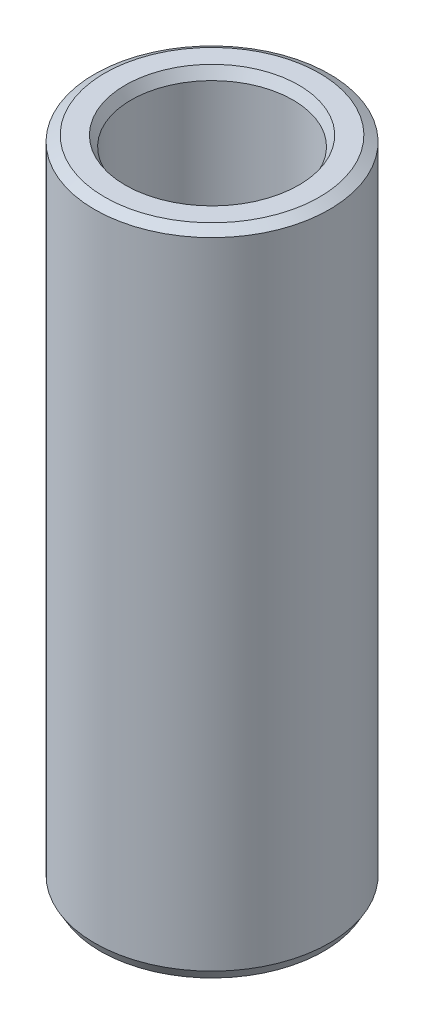
SolidWorks part; units mm, degrees
ref_plane "Front Plane" through (0, 0, 0) normal (0, 0, 1) x (1, 0, 0)
ref_plane "Top Plane" through (0, 0, 0) normal (0, 1, 0) x (1, 0, 0)
ref_plane "Right Plane" through (0, 0, 0) normal (1, 0, 0) x (0, 0, -1)
sketch "Sketch1" plane through (0, 0, 0) normal (0, 1, 0) x (1, 0, 0)
  circle A0 centre (0, 0) radius 57.5
  dimension "SLEEVE_OD" = 115
extrude "Boss-Extrude1" add sketch "Sketch1" along normal blind 318.8693
sketch "Sketch2" plane through (0, 0, 0) normal (0, 1, 0) x (1, 0, 0)
  circle A0 centre (0, 0) radius 39.6501
  dimension "BORE_D" = 79.3002
extrude "Cut-Extrude1" cut sketch "Sketch2" along normal through all
chamfer "Chamfer1" distance 2.8333 angle 60 4 edges at (0, 318.8693, 39.6501) (0, 0, 39.6501) (0, 0, 57.5) (0, 318.8693, 57.5) first distance on face at (0, 318.8693, 39.6501) first distance on face at (0, 0, 39.6501) first distance on face at (0, 318.8693, 57.5)
